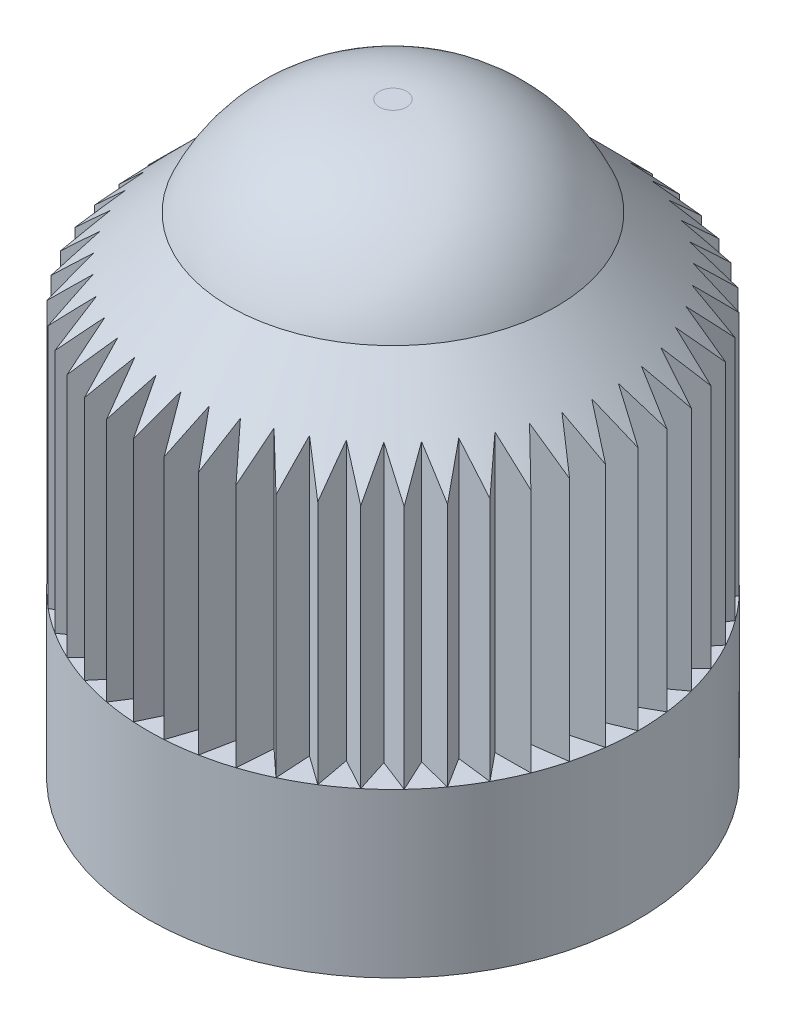
SolidWorks part; units mm, degrees
ref_plane "Спереди" through (0, 0, 0) normal (0, 0, 1) x (1, 0, 0)
ref_plane "Сверху" through (0, 0, 0) normal (0, 1, 0) x (1, 0, 0)
ref_plane "Справа" through (0, 0, 0) normal (1, 0, 0) x (0, 0, -1)
sketch "Sketch1" plane through (0, 0, 0) normal (0, 1, 0) x (1, 0, 0)
  circle A0 centre (0, 0) radius 7.5
  dimension "D1" = 15
extrude "Boss-Extrude1" add sketch "Sketch1" along normal blind 18
sketch "Sketch2" plane through (0, 0, 0) normal (0, -1, 0) x (1, 0, 0)
  circle A0 centre (0, 0) radius 6.5
  dimension "D1" = 13
extrude "Cut-Extrude1" cut sketch "Sketch2" against normal blind 3
sketch "Sketch3" plane through (0, 3, 0) normal (0, -1, 0) x (1, 0, 0)
  line L0 (-1.7426, -2.6839) -> (3.1363, -0.6354)
  line L1 (0.6968, -1.6596) -> (-1.2388, 2.9505) construction
  circle A0 centre (0, 0) radius 3.2 construction
  arc A1 (-1.7426, -2.6839) -> (3.1363, -0.6354) centre (0, 0) cw
  dimension "D1" = 6.4
  dimension "D2" = 5
extrude "Cut-Extrude2" cut sketch "Sketch3" against normal blind 12
chamfer "Chamfer1" distance 1 angle 30 1 edges at (0, 0, -6.5) first distance on face at (0, 3, -6.5)
sketch "Sketch4" plane through (0, 18, 0) normal (0, 1, 0) x (1, 0, 0)
  circle A0 centre (0, 0) radius 5
  dimension "D1" = 10
extrude "Cut-Extrude3" cut sketch "Sketch4" against normal blind 13 flip side to cut
chamfer "Chamfer2" distance 10 angle 45 1 edges at (0, 5, 5)
sketch "Sketch5" plane through (0, 18, 0) normal (0, 1, 0) x (1, 0, 0)
  line L0 (2.3986, -6.0413) -> (2.3244, -7.1307)
  line L1 (2.3244, -7.1307) -> (1.6225, -6.2942)
  line L2 (1.6225, -6.2942) -> (1.4124, -7.3658)
  line L3 (1.4124, -7.3658) -> (0.8208, -6.448)
  line L4 (0.8208, -6.448) -> (0.4781, -7.4847)
  line L5 (0.4781, -7.4847) -> (0.0062, -6.5)
  line L6 (0.0062, -6.5) -> (-0.4638, -7.4856)
  line L7 (-0.4638, -7.4856) -> (-0.8085, -6.4495)
  line L8 (-0.8085, -6.4495) -> (-1.3983, -7.3685)
  line L9 (-1.3983, -7.3685) -> (-1.6105, -6.2973)
  line L10 (-1.6105, -6.2973) -> (-2.3108, -7.1351)
  line L11 (-2.3108, -7.1351) -> (-2.3871, -6.0458)
  line L12 (-2.3871, -6.0458) -> (-3.1869, -6.7892)
  line L13 (-3.1869, -6.7892) -> (-3.126, -5.699)
  line L14 (-3.126, -5.699) -> (-4.0127, -6.3363)
  line L15 (-4.0127, -6.3363) -> (-3.8156, -5.2622)
  line L16 (-3.8156, -5.2622) -> (-4.7752, -5.7834)
  line L17 (-4.7752, -5.7834) -> (-4.445, -4.7425)
  line L18 (-4.445, -4.7425) -> (-5.4624, -5.1393)
  line L19 (-5.4624, -5.1393) -> (-5.0044, -4.148)
  line L20 (-5.0044, -4.148) -> (-6.0634, -4.4142)
  line L21 (-6.0634, -4.4142) -> (-5.4848, -3.4881)
  line L22 (-5.4848, -3.4881) -> (-6.5689, -3.6194)
  line L23 (-6.5689, -3.6194) -> (-5.8787, -2.7732)
  line L24 (-5.8787, -2.7732) -> (-6.9707, -2.7676)
  line L25 (-6.9707, -2.7676) -> (-6.18, -2.0145)
  line L26 (-6.18, -2.0145) -> (-7.2626, -1.8721)
  line L27 (-7.2626, -1.8721) -> (-6.3837, -1.2241)
  line L28 (-6.3837, -1.2241) -> (-7.44, -0.9471)
  line L29 (-7.44, -0.9471) -> (-6.4868, -0.4143)
  line L30 (-6.4868, -0.4143) -> (-7.5, -0.0071)
  line L31 (-7.5, -0.0071) -> (-6.4876, 0.402)
  line L32 (-6.4876, 0.402) -> (-7.4418, 0.9329)
  line L33 (-7.4418, 0.9329) -> (-6.386, 1.2119)
  line L34 (-6.386, 1.2119) -> (-7.2661, 1.8583)
  line L35 (-7.2661, 1.8583) -> (-6.1838, 2.0027)
  line L36 (-6.1838, 2.0027) -> (-6.9759, 2.7543)
  line L37 (-6.9759, 2.7543) -> (-5.884, 2.762)
  line L38 (-5.884, 2.762) -> (-6.5757, 3.6069)
  line L39 (-6.5757, 3.6069) -> (-5.4914, 3.4777)
  line L40 (-5.4914, 3.4777) -> (-6.0718, 4.4026)
  line L41 (-6.0718, 4.4026) -> (-5.0123, 4.1385)
  line L42 (-5.0123, 4.1385) -> (-5.4721, 5.1289)
  line L43 (-5.4721, 5.1289) -> (-4.4541, 4.7341)
  line L44 (-4.4541, 4.7341) -> (-4.7862, 5.7743)
  line L45 (-4.7862, 5.7743) -> (-3.8256, 5.255)
  line L46 (-3.8256, 5.255) -> (-4.0247, 6.3286)
  line L47 (-4.0247, 6.3286) -> (-3.1368, 5.693)
  line L48 (-3.1368, 5.693) -> (-3.1998, 6.7832)
  line L49 (-3.1998, 6.7832) -> (-2.3986, 6.0413)
  line L50 (-2.3986, 6.0413) -> (-2.3244, 7.1307)
  line L51 (-2.3244, 7.1307) -> (-1.6225, 6.2942)
  line L52 (-1.6225, 6.2942) -> (-1.4124, 7.3658)
  line L53 (-1.4124, 7.3658) -> (-0.8208, 6.448)
  line L54 (-0.8208, 6.448) -> (-0.4781, 7.4847)
  line L55 (-0.4781, 7.4847) -> (-0.0062, 6.5)
  line L56 (-0.0062, 6.5) -> (0.4638, 7.4856)
  line L57 (0.4638, 7.4856) -> (0.8085, 6.4495)
  line L58 (0.8085, 6.4495) -> (1.3983, 7.3685)
  line L59 (1.3983, 7.3685) -> (1.6105, 6.2973)
  line L60 (1.6105, 6.2973) -> (2.3108, 7.1351)
  line L61 (2.3108, 7.1351) -> (2.3871, 6.0458)
  line L62 (2.3871, 6.0458) -> (3.1869, 6.7892)
  line L63 (3.1869, 6.7892) -> (3.126, 5.699)
  line L64 (3.126, 5.699) -> (4.0127, 6.3363)
  line L65 (4.0127, 6.3363) -> (3.8156, 5.2622)
  line L66 (3.8156, 5.2622) -> (4.7752, 5.7834)
  line L67 (4.7752, 5.7834) -> (4.445, 4.7425)
  line L68 (4.445, 4.7425) -> (5.4624, 5.1393)
  line L69 (5.4624, 5.1393) -> (5.0044, 4.148)
  line L70 (5.0044, 4.148) -> (6.0634, 4.4142)
  line L71 (6.0634, 4.4142) -> (5.4848, 3.4881)
  line L72 (5.4848, 3.4881) -> (6.5689, 3.6194)
  line L73 (6.5689, 3.6194) -> (5.8787, 2.7732)
  line L74 (5.8787, 2.7732) -> (6.9707, 2.7676)
  line L75 (6.9707, 2.7676) -> (6.18, 2.0145)
  line L76 (6.18, 2.0145) -> (7.2626, 1.8721)
  line L77 (7.2626, 1.8721) -> (6.3837, 1.2241)
  line L78 (6.3837, 1.2241) -> (7.44, 0.9471)
  line L79 (7.44, 0.9471) -> (6.4868, 0.4143)
  line L80 (6.4868, 0.4143) -> (7.5, 0.0071)
  line L81 (7.5, 0.0071) -> (6.4876, -0.402)
  line L82 (6.4876, -0.402) -> (7.4418, -0.9329)
  line L83 (7.4418, -0.9329) -> (6.386, -1.2119)
  line L84 (6.386, -1.2119) -> (7.2661, -1.8583)
  line L85 (7.2661, -1.8583) -> (6.1838, -2.0027)
  line L86 (6.1838, -2.0027) -> (6.9759, -2.7543)
  line L87 (6.9759, -2.7543) -> (5.884, -2.762)
  line L88 (5.884, -2.762) -> (6.5757, -3.6069)
  line L89 (6.5757, -3.6069) -> (5.4914, -3.4777)
  line L90 (5.4914, -3.4777) -> (6.0718, -4.4026)
  line L91 (6.0718, -4.4026) -> (5.0123, -4.1385)
  line L92 (5.0123, -4.1385) -> (5.4721, -5.1289)
  line L93 (5.4721, -5.1289) -> (4.4541, -4.7341)
  line L94 (4.4541, -4.7341) -> (4.7862, -5.7743)
  line L95 (4.7862, -5.7743) -> (3.8256, -5.255)
  line L96 (3.8256, -5.255) -> (4.0247, -6.3286)
  line L97 (4.0247, -6.3286) -> (3.1368, -5.693)
  line L98 (3.1368, -5.693) -> (3.1998, -6.7832)
  line L99 (3.1998, -6.7832) -> (2.3986, -6.0413)
  circle A0 centre (0, 0) radius 6.5 construction
  circle A2 centre (0, 0) radius 7.5 construction
  point P3 (0, 0)
  point P5 (0, 0)
  point P7 (0, 0)
  point P156 (0, 0)
  dimension "D1" = 13
  dimension "D2" = 50
extrude "Cut-Extrude4" cut sketch "Sketch5" against normal blind 13 flip side to cut
fillet "Fillet1" radius 5 1 edges at (0, 18, 5)
